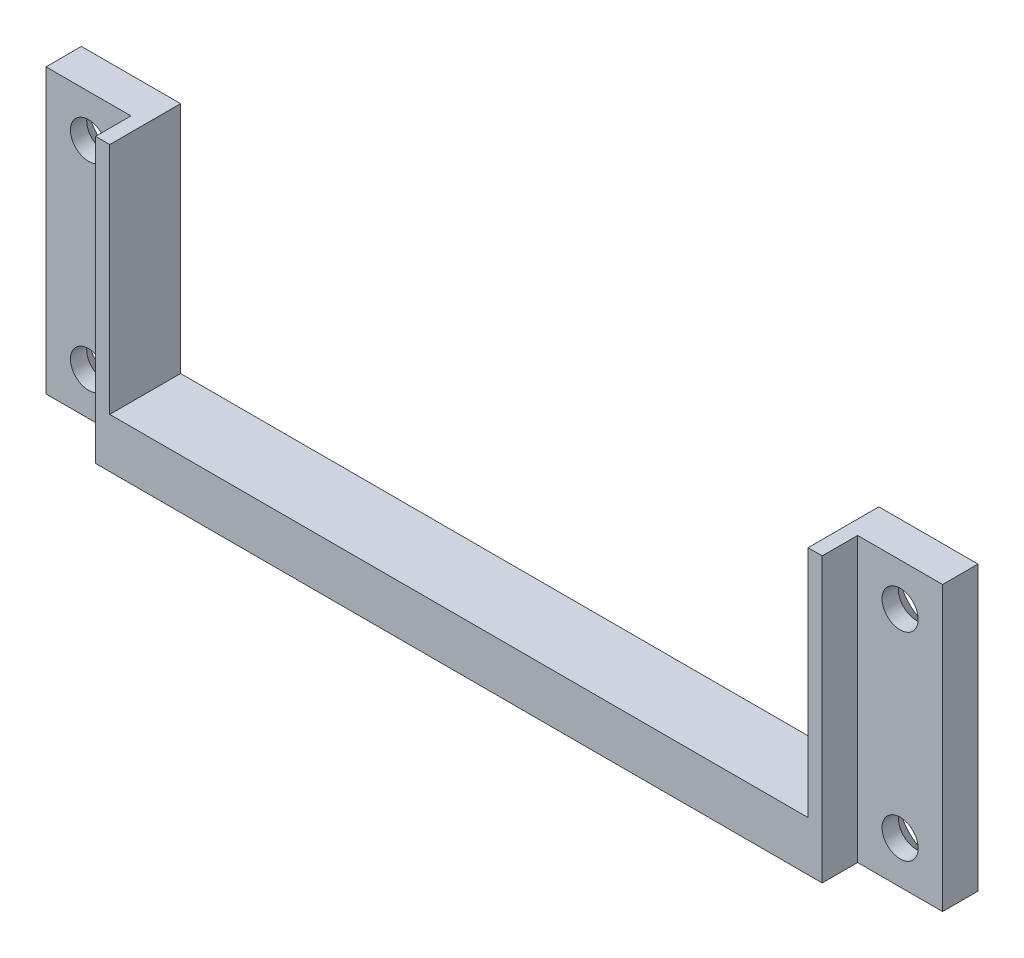
SolidWorks part; units mm, degrees
ref_plane "Plan de face" through (0, 0, 0) normal (0, 0, 1) x (1, 0, 0)
ref_plane "Plan de dessus" through (0, 0, 0) normal (0, 1, 0) x (1, 0, 0)
ref_plane "Plan de droite" through (0, 0, 0) normal (1, 0, 0) x (0, 0, -1)
sketch "Esquisse1" plane through (0, 0, 0) normal (0, 0, 1) x (1, 0, 0)
  line L1 (-17.4678, 19.1867) -> (85.1322, 19.1867)
  line L2 (-17.4678, 19.1867) -> (-17.4678, -15.8133)
  line L3 (-17.4678, -15.8133) -> (85.1322, -15.8133)
  line L4 (85.1322, 19.1867) -> (85.1322, -15.8133)
  dimension "D1" = 35
  dimension "D2" = 102.6
extrude "Boss.-Extru.1" add sketch "Esquisse1" along normal blind 10 and the other way blind 0.0001
sketch "Esquisse4" plane through (0, 19.1867, 0) normal (0, 1, 0) x (1, 0, 0)
  line L1 (-15.4678, -51.5999) -> (83.1322, -51.5999)
  line L2 (-15.4678, -51.5999) -> (-15.4678, 0.0001)
  line L3 (-15.4678, 0.0001) -> (83.1322, 0.0001)
  line L4 (83.1322, -51.5999) -> (83.1322, 0.0001)
  line L5 (-17.4678, -10) -> (-17.4678, 0.0001) construction
  line L6 (85.1322, -10) -> (85.1322, 0.0001) construction
  line L7 (85.1322, 0.0001) -> (-17.4678, 0.0001) construction
  dimension "D1" = 51.6
  dimension "D2" = 98.6
  dimension "D3" = 0
  dimension "D4" = 2
  dimension "D5" = 2
extrude "Enlèv. mat.-Extru.2" cut sketch "Esquisse4" against normal blind 33
sketch "Esquisse19" plane through (0, -15.8133, 0) normal (0, -1, 0) x (1, 0, 0)
  line L1 (85.1322, -0.0001) -> (-17.4678, -0.0001)
  line L2 (85.1322, -0.0001) -> (85.1322, 10)
  line L3 (85.1322, 10) -> (-17.4678, 10)
  line L4 (-17.4678, -0.0001) -> (-17.4678, 10)
extrude "Boss.-Extru.4" add sketch "Esquisse19" along normal blind 5
sketch "Esquisse21" plane through (-17.4678, 0, 0) normal (-1, 0, 0) x (0, 0, 1)
  line L0 (10, -20.8133) -> (-0.0001, -20.8133) construction
  line L1 (-0.0001, 19.1867) -> (4.9999, 19.1867)
  line L2 (-0.0001, 19.1867) -> (-0.0001, -20.8133)
  line L3 (-0.0001, -20.8133) -> (4.9999, -20.8133)
  line L4 (4.9999, 19.1867) -> (4.9999, -20.8133)
  dimension "D1" = 5
extrude "Boss.-Extru.5" add sketch "Esquisse21" along normal blind 12
sketch "Esquisse22" plane through (85.1322, 0, 0) normal (1, 0, 0) x (0, 0, -1)
  line L0 (0.0001, -20.8133) -> (-10, -20.8133) construction
  line L1 (0.0001, 19.1867) -> (-4.9999, 19.1867)
  line L2 (0.0001, 19.1867) -> (0.0001, -20.8133)
  line L3 (0.0001, -20.8133) -> (-4.9999, -20.8133)
  line L4 (-4.9999, 19.1867) -> (-4.9999, -20.8133)
  dimension "D1" = 5
extrude "Boss.-Extru.6" add sketch "Esquisse22" along normal blind 12
sketch "Esquisse23" plane through (0, 0, -0.0001) normal (0, 0, -1) x (-1, 0, 0)
  line L0 (-97.1322, -20.8133) -> (-97.1322, 19.1867) construction
  line L2 (-97.1322, 19.1867) -> (-83.1322, 19.1867) construction
  line L3 (29.4678, -20.8133) -> (-97.1322, -20.8133) construction
  line L4 (29.4678, 19.1867) -> (29.4678, -20.8133) construction
  line L5 (15.4678, 19.1867) -> (29.4678, 19.1867) construction
  circle A0 centre (-91.1322, 13.1867) radius 5.25
  circle A1 centre (-91.1322, -14.8133) radius 5.25
  circle A2 centre (23.4678, 13.1867) radius 5.25
  circle A3 centre (23.4678, -14.8133) radius 5.25
  dimension "D3" = 10.5
  dimension "D10" = 10.5
  dimension "D11" = 10.5
  dimension "D12" = 10.5
  dimension "D1" = 6
  dimension "D2" = 6
  dimension "D4" = 6
  dimension "D5" = 6
  dimension "D6" = 6
  dimension "D7" = 6
  dimension "D8" = 6
  dimension "D9" = 6
hole_wizard "Fraisage pour vis à tête fraisée bombée #51" positions "Esquisse3D1" profile "Esquisse24" countersink size "#5" standard "Ansi Inch" end condition through all
sketch3d "Esquisse3D1"
  point P0 (91.1322, 13.1867, -0.0001)
  point P3 (91.1322, -14.8133, -0.0001)
  point P6 (-23.4678, 13.1867, -0.0001)
  point P9 (-23.4678, -14.8133, -0.0001)
sketch "Esquisse24" plane through (91.1322, 13.1867, -0.0001) normal (1, 0, 0) x (0, 1, 0)
  line L0 (0, 0) -> (0, 10.0001)
  line L1 (0, 10.0001) -> (2.55, 10.0001)
  line L2 (2.55, 10.0001) -> (2.55, 2.7)
  line L3 (2.55, 2.7) -> (5.25, 0)
  line L5 (5.25, 0) -> (0, 0)
  line L6 (-2.55, 2.7) -> (-5.25, 0) construction
  line L11 (0, -6.35) -> (0, 107.95) construction
  dimension "Diamètre du perçage jusqu'au prochain" = 5.1
  dimension "Profondeur du perçage jusqu'au prochain" = 10.0001
  dimension "Diamètre du fraisage entrant" = 10.5
  dimension "Angle du fraisage entrant" = 90
